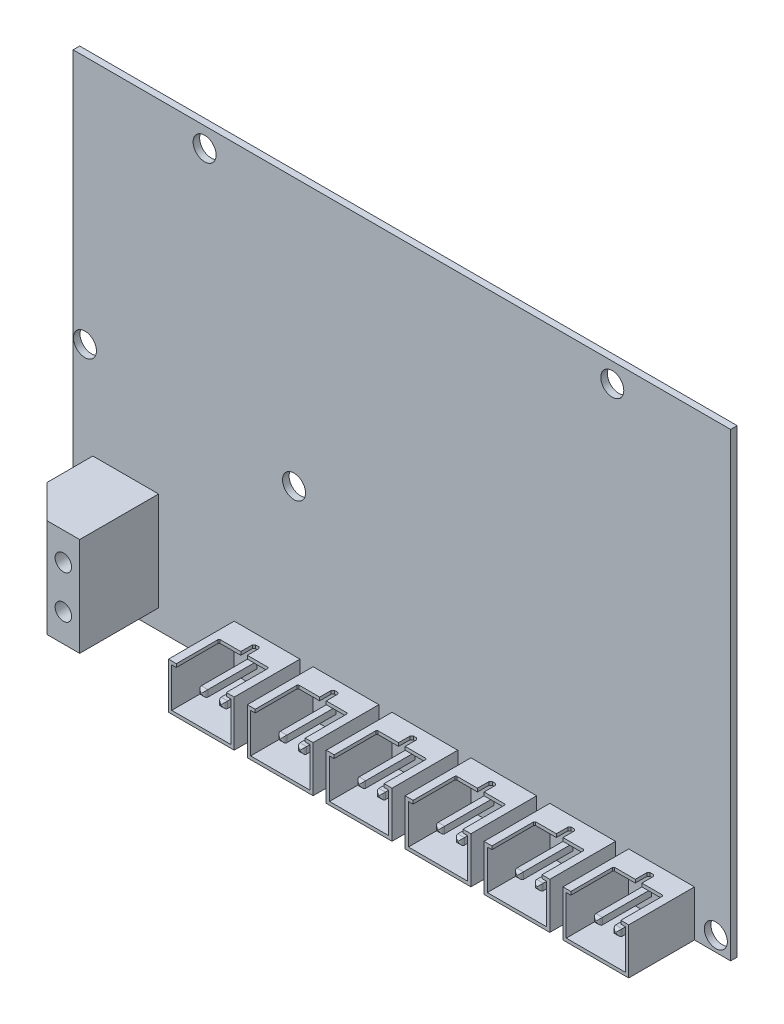
SolidWorks part; units mm, degrees
ref_plane "Alzado" through (0, 0, 0) normal (0, 0, 1) x (1, 0, 0)
ref_plane "Planta" through (0, 0, 0) normal (0, 1, 0) x (1, 0, 0)
ref_plane "Vista lateral" through (0, 0, 0) normal (1, 0, 0) x (0, 0, -1)
sketch "Croquis1" plane through (0, 0, 0) normal (0, 0, 1) x (1, 0, 0)
  line L1 (-63.5082, 38.0543) -> (36.4918, 38.0543)
  line L2 (-63.5082, 38.0543) -> (-63.5082, -31.9457)
  line L3 (-63.5082, -31.9457) -> (36.4918, -31.9457)
  line L4 (36.4918, 38.0543) -> (36.4918, -31.9457)
  circle A0 centre (-61.7082, 0.1543) radius 1.75
  circle A1 centre (-43.5082, 35.0543) radius 1.75
  circle A2 centre (18.4918, 35.0543) radius 1.75
  circle A3 centre (-29.9082, -2.6457) radius 1.75
  circle A4 centre (34.2418, -29.6957) radius 1.75
  dimension "D4" = 3.5
  dimension "D1" = 70
  dimension "D2" = 100
  dimension "D3" = 70
  dimension "D5" = 1.8
  dimension "D6" = 32.1
  dimension "D7" = 20
  dimension "D8" = 3
  dimension "D9" = 29.3
  dimension "D10" = 33.6
  dimension "D11" = 2.25
  dimension "D12" = 2.25
  dimension "D13" = 3
  dimension "D14" = 18
extrude "Saliente-Extruir1" add sketch "Croquis1" along normal blind 1
ref_plane "Plano1" through (0, 0, 1.5) normal (0, 0, 1) x (1, 0, 0)
sketch "Croquis3" plane through (0, 0, 1.5) normal (0, 0, 1) x (1, 0, 0)
  line L1 (31.4918, -24.4457) -> (21.4918, -24.4457)
  line L2 (31.4918, -24.4457) -> (31.4918, -31.4457)
  line L3 (31.4918, -31.4457) -> (21.4918, -31.4457)
  line L4 (21.4918, -24.4457) -> (21.4918, -31.4457)
  dimension "D3" = 7
  dimension "D4" = 10
extrude "Saliente-Extruir3" add sketch "Croquis3" along normal blind 10 separate body
shell "Vaciado3" thickness 0.5 removed face at (26.4918, -27.9457, 11.5)
sketch "Croquis5" plane through (0, -24.4457, 0) normal (0, 1, 0) x (1, 0, 0)
  line L0 (22.6918, -11.5) -> (22.6918, -5.15)
  line L1 (31.4918, -11.5) -> (21.4918, -11.5) construction
  line L2 (22.8418, -5) -> (25.9918, -5)
  line L3 (25.9918, -5) -> (25.9918, -3.25)
  line L4 (26.2418, -3) -> (26.7418, -3)
  line L5 (26.9918, -3.25) -> (26.9918, -5)
  line L6 (26.9918, -5) -> (30.1418, -5)
  line L7 (30.2918, -5.15) -> (30.2918, -11.5)
  line L8 (30.2918, -11.5) -> (22.6918, -11.5)
  line L9 (25.9918, -3.25) -> (26.2418, -3)
  line L10 (21.4918, -11.5) -> (22.6918, -11.5) construction
  line L11 (30.2918, -11.5) -> (31.4918, -11.5) construction
  line L12 (26.7418, -3) -> (26.9918, -3.25)
  line L13 (22.6918, -5.15) -> (22.8418, -5)
  line L14 (30.1418, -5) -> (30.2918, -5.15)
  point P1 (22.6918, -5)
  point P6 (25.9918, -3)
  point P7 (26.9918, -3)
  point P9 (30.2918, -5)
  dimension "D1" = 1.2
  dimension "D2" = 1
  dimension "D3" = 2
  dimension "D4" = 6.5
extrude "Cortar-Extruir1" cut sketch "Croquis5" against normal blind 1
sketch "Croquis6" plane through (0, 0, 2) normal (0, 0, 1) x (1, 0, 0)
  line L0 (24.4918, -28.4604) -> (21.9918, -28.4604) construction
  line L1 (24.4918, -27.4604) -> (25.4918, -27.4604)
  line L2 (24.4918, -27.4604) -> (24.4918, -28.4604)
  line L3 (24.4918, -28.4604) -> (25.4918, -28.4604)
  line L4 (25.4918, -27.4604) -> (25.4918, -28.4604)
  line L5 (27.4918, -27.4604) -> (28.4918, -27.4604)
  line L6 (27.4918, -27.4604) -> (27.4918, -28.4604)
  line L7 (27.4918, -28.4604) -> (28.4918, -28.4604)
  line L8 (28.4918, -27.4604) -> (28.4918, -28.4604)
  line L9 (21.9918, -24.9457) -> (21.9918, -30.9457) construction
  line L10 (28.4918, -28.4604) -> (30.9918, -28.4604) construction
  line L12 (30.9918, -30.9457) -> (30.9918, -24.9457) construction
  dimension "D1" = 2
  dimension "D2" = 1
extrude "Saliente-Extruir4" add sketch "Croquis6" along normal blind 8
fillet "Redondeo1" radius 0.5 8 edges at (27.9918, -27.4604, 10) (28.4918, -27.9604, 10) (27.9918, -28.4604, 10) (27.4918, -27.9604, 10) (24.9918, -27.4604, 10) (25.4918, -27.9604, 10) (24.9918, -28.4604, 10) (24.4918, -27.9604, 10)
pattern_linear "MatrizL4" count 6 spacing 12 along (-1, 0, 0) of "Saliente-Extruir3"
shell "Vaciado4" thickness 0.5 removed face at (14.4918, -27.9457, 11.5)
shell "Vaciado5" thickness 0.5 removed face at (2.4918, -27.9457, 11.5)
shell "Vaciado6" thickness 0.5 removed face at (-9.5082, -27.9457, 11.5)
shell "Vaciado7" thickness 0.5 removed face at (-21.5082, -27.9457, 11.5)
shell "Vaciado8" thickness 0.5 removed face at (-33.5082, -27.9457, 11.5)
pattern_linear "MatrizL5" count 6 spacing 12 along (-1, 0, 0) of "Cortar-Extruir1"
pattern_linear "MatrizL6" count 6 spacing 12 along (-1, 0, 0) of "Saliente-Extruir4"
fillet "Redondeo2" radius 0.5 8 edges at (15.9918, -27.4604, 10) (16.4918, -27.9604, 10) (15.9918, -28.4604, 10) (15.4918, -27.9604, 10) (12.9918, -27.4604, 10) (13.4918, -27.9604, 10) (12.9918, -28.4604, 10) (12.4918, -27.9604, 10)
fillet "Redondeo3" radius 0.5 8 edges at (0.9918, -27.4604, 10) (1.4918, -27.9604, 10) (0.9918, -28.4604, 10) (0.4918, -27.9604, 10) (3.9918, -27.4604, 10) (4.4918, -27.9604, 10) (3.9918, -28.4604, 10) (3.4918, -27.9604, 10)
fillet "Redondeo4" radius 0.5 8 edges at (-11.0082, -27.4604, 10) (-10.5082, -27.9604, 10) (-11.0082, -28.4604, 10) (-11.5082, -27.9604, 10) (-8.0082, -27.4604, 10) (-7.5082, -27.9604, 10) (-8.0082, -28.4604, 10) (-8.5082, -27.9604, 10)
fillet "Redondeo5" radius 0.5 8 edges at (-23.0082, -27.4604, 10) (-22.5082, -27.9604, 10) (-23.0082, -28.4604, 10) (-23.5082, -27.9604, 10) (-20.0082, -27.4604, 10) (-19.5082, -27.9604, 10) (-20.0082, -28.4604, 10) (-20.5082, -27.9604, 10)
fillet "Redondeo6" radius 0.5 8 edges at (-35.0082, -27.4604, 10) (-34.5082, -27.9604, 10) (-35.0082, -28.4604, 10) (-35.5082, -27.9604, 10) (-32.0082, -27.4604, 10) (-31.5082, -27.9604, 10) (-32.0082, -28.4604, 10) (-32.5082, -27.9604, 10)
sketch "Croquis13" plane through (0, 0, 1.5) normal (0, 0, 1) x (1, 0, 0)
  line L0 (-63.5082, 38.0543) -> (-63.5082, -31.9457) construction
  line L1 (-60.0082, -28.4457) -> (-50.0082, -28.4457)
  line L2 (-60.0082, -28.4457) -> (-60.0082, -13.4457)
  line L3 (-60.0082, -13.4457) -> (-50.0082, -13.4457)
  line L4 (-50.0082, -28.4457) -> (-50.0082, -13.4457)
  line L5 (-63.5082, -31.9457) -> (36.4918, -31.9457) construction
  dimension "D1" = 10
  dimension "D2" = 15
  dimension "D3" = 3.5
  dimension "D4" = 3.5
extrude "Saliente-Extruir5" add sketch "Croquis13" along normal blind 12 separate body
chamfer "Chaflán1" distance 5 angle 45 1 edges at (-60.0082, -20.9457, 13.5)
sketch "Croquis14" plane through (0, 0, 13.5) normal (0, 0, 1) x (1, 0, 0)
  line L0 (-55.0082, -28.4457) -> (-50.0082, -28.4457) construction
  point P0 (-52.4888, -16.2448)
  point P1 (-52.4888, -25.2101)
  dimension "D1" = 3.2356
sketch "Croquis15" plane through (0, 0, 13.5) normal (0, 0, 1) x (1, 0, 0)
  line L0 (-52.4909, -17.6957) -> (-52.4909, -24.1957) construction
  line L1 (-52.4909, -17.6957) -> (-52.5082, -13.4457) construction
  line L2 (-50.0082, -13.4457) -> (-55.0082, -13.4457) construction
  line L3 (-52.4909, -24.1957) -> (-52.5082, -28.4457) construction
  line L4 (-55.0082, -28.4457) -> (-50.0082, -28.4457) construction
  circle A0 centre (-52.4909, -17.6957) radius 1.25
  circle A1 centre (-52.4909, -24.1957) radius 1.25
  dimension "D2" = 2.5
  dimension "D1" = 6.5
extrude "Cortar-Extruir2" cut sketch "Croquis15" against normal blind 9
sketch "Croquis16" plane through (-60.0082, 0, -60.0082) normal (1, 0, 0) x (0, 0, -1)
  line L0 (-64.9909, -17.6957) -> (-64.9909, -24.1957) construction
  line L1 (-64.9909, -17.6957) -> (-65.0082, -13.4457) construction
  line L3 (-64.9909, -24.1957) -> (-65.0082, -28.4457) construction
  line L5 (-68.5082, -13.4457) -> (-61.5082, -13.4457) construction
  line L6 (-65.0082, -13.4457) -> (-65.0082, -28.4457) construction
  line L7 (-68.5082, -28.4457) -> (-61.5082, -28.4457) construction
  circle A0 centre (-64.9909, -17.6957) radius 1.25
  circle A1 centre (-64.9909, -24.1957) radius 1.25
  dimension "D2" = 2.5
  dimension "D1" = 6.5
extrude "Cortar-Extruir3" cut sketch "Croquis16" along normal blind 9
